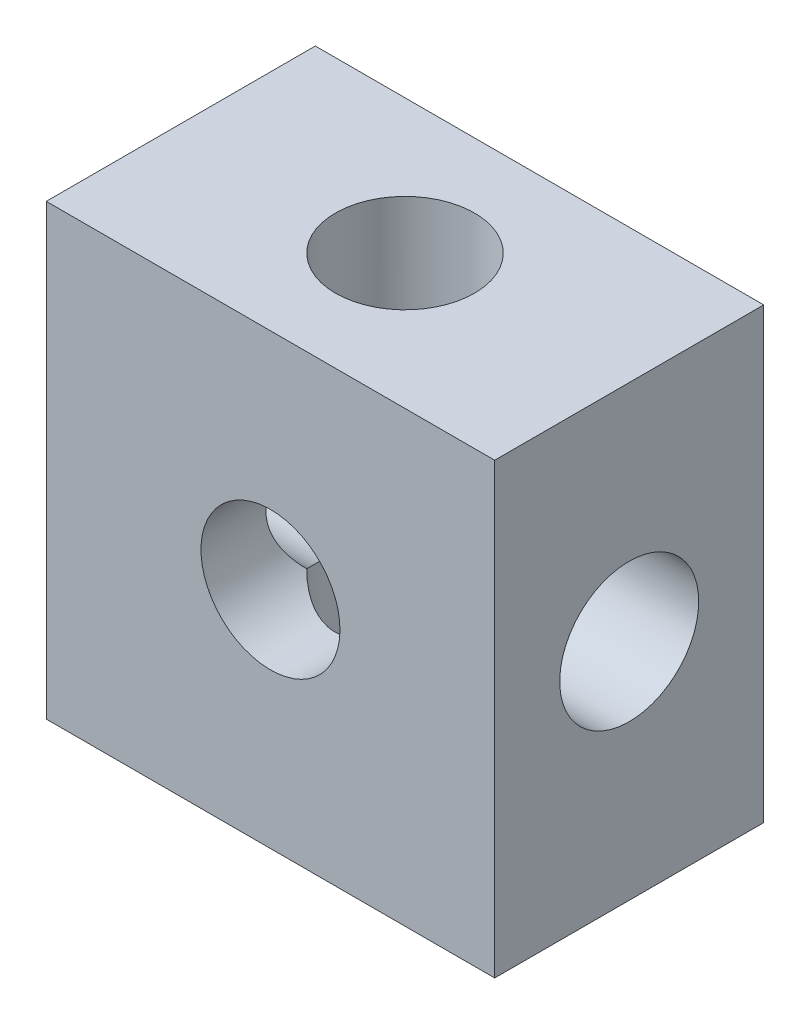
SolidWorks part; units mm, degrees
material "6063-O"
ref_plane "前视基准面" through (0, 0, 0) normal (0, 0, 1) x (1, 0, 0)
ref_plane "上视基准面" through (0, 0, 0) normal (0, 1, 0) x (1, 0, 0)
ref_plane "右视基准面" through (0, 0, 0) normal (1, 0, 0) x (0, 0, -1)
sketch "草图1" plane through (0, 0, 0) normal (0, 1, 0) x (1, 0, 0)
  line L1 (0, 0) -> (10, 0)
  line L2 (0, 0) -> (0, 6)
  line L3 (0, 6) -> (10, 6)
  line L4 (10, 0) -> (10, 6)
  dimension "D1" = 10
  dimension "D2" = 6
extrude "凸台-拉伸1" add sketch "草图1" along normal blind 10
sketch "草图2" plane through (0, 10, 0) normal (0, 1, 0) x (1, 0, 0)
  line L0 (0, 6) -> (10, 0) construction
  line L1 (0, 0) -> (10, 0) construction
  line L2 (10, 0) -> (10, 6) construction
  circle A0 centre (5, 3) radius 1.55
  dimension "D1" = 3.1
extrude "切除-拉伸1" cut sketch "草图2" against normal blind 10
sketch "草图3" plane through (0, 0, 0) normal (0, 0, 1) x (1, 0, 0)
  line L0 (0, 10) -> (10, 0) construction
  line L1 (0, 0) -> (10, 0) construction
  circle A0 centre (5, 5) radius 1.55
  dimension "D1" = 3.1
extrude "切除-拉伸2" cut sketch "草图3" against normal blind 10
sketch "草图4" plane through (10, 0, 0) normal (1, 0, 0) x (0, 0, -1)
  line L0 (0, 10) -> (6, 0) construction
  circle A0 centre (3, 5) radius 1.55
  dimension "D1" = 3.1
extrude "切除-拉伸3" cut sketch "草图4" against normal blind 10
